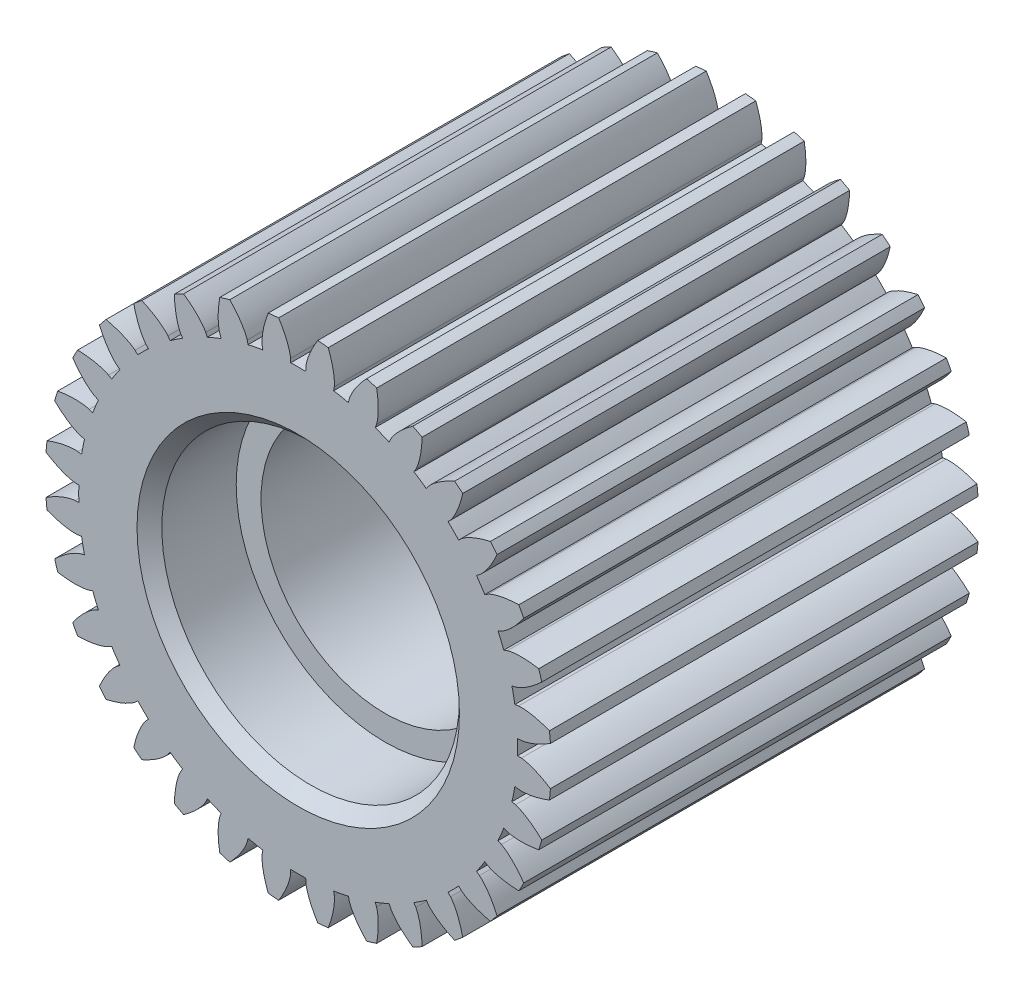
SolidWorks part; units mm, degrees
material "PLA"
ref_plane "Front Plane" through (0, 0, 0) normal (0, 0, 1) x (1, 0, 0)
ref_plane "Top Plane" through (0, 0, 0) normal (0, 1, 0) x (1, 0, 0)
ref_plane "Right Plane" through (0, 0, 0) normal (1, 0, 0) x (0, 0, -1)
sketch "Sketch1" plane through (0, 0, 0) normal (0, 0, 1) x (1, 0, 0)
  circle A0 centre (0, 0) radius 15
  dimension "D1" = 30
extrude "Boss-Extrude1" add sketch "Sketch1" along normal mid plane 17.2389
sketch "Sketch2" plane through (0, 0, 0) normal (0, 0, 1) x (1, 0, 0)
  line L0 (0, 0) -> (14.3977, 0.2566) construction
  line L1 (0, 0) -> (14.4, 0) construction
  line L2 (0, 0) -> (14.3977, -0.2566) construction
  line L3 (13.527, -0.2411) -> (13.6478, -0.2432)
  line L4 (13.5294, 0.2411) -> (13.6478, 0.2432)
  circle A0 centre (0, 0) radius 14.4 construction
  circle A1 centre (0, 0) radius 13.5316 construction
  circle A2 centre (0, 0) radius 13.65
  circle A3 centre (0, 0) radius 15 construction
  circle A4 centre (0, 0) radius 15
  spline S0 degree 4 poles (13.5294, 0.2411) (13.534, 0.2413) (13.547, 0.2419) (13.5715, 0.2439) (13.6113, 0.2483) (13.662, 0.2556) (13.7273, 0.267) (13.8039, 0.2829) (13.8878, 0.303) (13.9786, 0.3276) (14.0688, 0.3547) (14.1584, 0.3839) (14.2472, 0.4152) (14.3542, 0.4554) (14.4819, 0.507) (14.6298, 0.5722) (14.7962, 0.6518) (14.964, 0.7391) (15.1277, 0.8299) (15.2913, 0.9272) (15.4482, 1.0254) (15.6092, 1.1331) (15.7568, 1.2354) (15.9198, 1.3563) (16.0506, 1.4557) (16.2205, 1.5933) (16.32, 1.6765) (16.4355, 1.7761) (16.4863, 1.8215) (16.5176, 1.8494) knots 0 0 0 0 0 0.005377 0.015084 0.028532 0.04661 0.064855 0.092111 0.119476 0.146842 0.174209 0.201575 0.228941 0.256307 0.307035 0.361767 0.4165 0.471232 0.525964 0.580697 0.635429 0.690161 0.744894 0.799626 0.854358 0.909091 0.954545 1 1 1 1 1 construction
  spline S1 degree 4 poles (13.5294, 0.2411) (13.534, 0.2413) (13.547, 0.2419) (13.5715, 0.2439) (13.6113, 0.2483) (13.662, 0.2556) (13.7273, 0.267) (13.8039, 0.2829) (13.8878, 0.303) (13.9786, 0.3276) (14.0688, 0.3547) (14.1584, 0.3839) (14.2472, 0.4152) (14.3542, 0.4554) (14.4819, 0.507) (14.6298, 0.5722) (14.7962, 0.6518) (14.964, 0.7391) (15.1277, 0.8299) (15.2913, 0.9272) (15.4482, 1.0254) (15.6092, 1.1331) (15.7568, 1.2354) (15.9198, 1.3563) (16.0506, 1.4557) (16.1836, 1.5634) (16.2481, 1.6166) (16.2809, 1.6441) knots 0 0 0 0 0 0.005377 0.015084 0.028532 0.04661 0.064855 0.092111 0.119476 0.146842 0.174209 0.201575 0.228941 0.256307 0.307035 0.361767 0.4165 0.471232 0.525964 0.580697 0.635429 0.690161 0.744894 0.799626 0.854358 0.909091 0.909091 0.909091 0.909091 0.909091
  spline S2 degree 4 poles (13.527, -0.2411) (13.5316, -0.2412) (13.5446, -0.2419) (13.569, -0.2438) (13.6089, -0.2483) (13.6595, -0.2556) (13.7248, -0.2669) (13.8015, -0.2828) (13.8853, -0.3029) (13.9762, -0.3276) (14.0664, -0.3546) (14.1559, -0.3839) (14.2447, -0.4151) (14.3518, -0.4554) (14.4794, -0.507) (14.6274, -0.5722) (14.7937, -0.6518) (14.9616, -0.739) (15.1253, -0.8298) (15.2888, -0.9272) (15.4458, -1.0254) (15.6068, -1.1331) (15.7543, -1.2354) (15.9173, -1.3563) (16.0481, -1.4556) (16.218, -1.5932) (16.3175, -1.6764) (16.4331, -1.776) (16.4838, -1.8215) (16.5151, -1.8494) knots 0 0 0 0 0 0.005377 0.015084 0.028532 0.04661 0.064855 0.092111 0.119476 0.146842 0.174209 0.201575 0.228941 0.256307 0.307035 0.361767 0.4165 0.471232 0.525964 0.580697 0.635429 0.690161 0.744894 0.799626 0.854358 0.909091 0.954545 1 1 1 1 1 construction
  spline S3 degree 4 poles (13.527, -0.2411) (13.5316, -0.2412) (13.5446, -0.2419) (13.569, -0.2438) (13.6089, -0.2483) (13.6595, -0.2556) (13.7248, -0.2669) (13.8015, -0.2828) (13.8853, -0.3029) (13.9762, -0.3276) (14.0664, -0.3546) (14.1559, -0.3839) (14.2447, -0.4151) (14.3518, -0.4554) (14.4794, -0.507) (14.6274, -0.5722) (14.7937, -0.6518) (14.9616, -0.739) (15.1253, -0.8298) (15.2888, -0.9272) (15.4458, -1.0254) (15.6068, -1.1331) (15.7543, -1.2354) (15.9173, -1.3563) (16.0481, -1.4556) (16.1812, -1.5634) (16.2456, -1.6166) (16.2784, -1.6441) knots 0 0 0 0 0 0.005377 0.015084 0.028532 0.04661 0.064855 0.092111 0.119476 0.146842 0.174209 0.201575 0.228941 0.256307 0.307035 0.361767 0.4165 0.471232 0.525964 0.580697 0.635429 0.690161 0.744894 0.799626 0.854358 0.909091 0.909091 0.909091 0.909091 0.909091
  dimension "D1" = 28.8
  dimension "D2" = 27.0631
  dimension "D3" = 27.3
  dimension "D4" = 1.021
  dimension "D5" = 1.021
extrude "Cut-Extrude1" cut sketch "Sketch2" against normal through all both and the other way through all
pattern_circular "CirPattern2" count 48 over 360 about axis through (0, 0, 8.6195) along (0, 0, -1) of "Cut-Extrude1"
sketch "Sketch3" plane through (0, 0, 8.6195) normal (0, 0, 1) x (1, 0, 0)
  circle A0 centre (0, 0) radius 5
  dimension "D1" = 10
sketch "Sketch4" plane through (0, 0, -8.6195) normal (0, 0, -1) x (-1, 0, 0)
  circle A0 centre (0, 0) radius 10.2
  dimension "D1" = 20.4
extrude "Boss-Extrude2" add sketch "Sketch4" along normal blind 17.2389
sketch "Sketch5" plane through (0, 0, -25.8584) normal (0, 0, -1) x (-1, 0, 0)
  line L0 (0, 0) -> (10.2, 0) construction
  line L1 (0, 0) -> (10.194, 0.3486) construction
  line L2 (0, 0) -> (10.194, -0.3486) construction
  line L3 (8.9952, 0.3076) -> (8.8448, 0.3025)
  line L4 (8.9952, -0.3076) -> (8.8448, -0.3025)
  circle A0 centre (0, 0) radius 9.021 construction
  circle A1 centre (0, 0) radius 8.85
  arc A2 (10.1694, -0.7895) -> (10.1694, 0.7895) centre (0, 0) ccw
  spline S0 degree 4 poles (8.9952, 0.3076) (8.9983, 0.3078) (9.0069, 0.3083) (9.0232, 0.3099) (9.0497, 0.3133) (9.0989, 0.3212) (9.1575, 0.3334) (9.2234, 0.3498) (9.2937, 0.3702) (9.3535, 0.3892) (9.4129, 0.4097) (9.4717, 0.4314) (9.5427, 0.4594) (9.6272, 0.4952) (9.7251, 0.5403) (9.8351, 0.5952) (9.9461, 0.6552) (10.0542, 0.7175) (10.1621, 0.7842) (10.2657, 0.8513) (10.3718, 0.9249) (10.4691, 0.9947) (10.5764, 1.077) (10.6625, 1.1447) (10.7743, 1.2383) (10.8397, 1.2948) (10.9156, 1.3625) (10.9489, 1.3933) (10.9695, 1.4123) knots 0 0 0 0 0 0.005377 0.015084 0.028532 0.04661 0.092111 0.119476 0.146842 0.174209 0.201575 0.228941 0.256307 0.307035 0.361767 0.4165 0.471232 0.525964 0.580697 0.635429 0.690161 0.744894 0.799626 0.854358 0.909091 0.954545 1 1 1 1 1 construction
  spline S1 degree 4 poles (8.9952, 0.3076) (8.9983, 0.3078) (9.0069, 0.3083) (9.0232, 0.3099) (9.0497, 0.3133) (9.0989, 0.3212) (9.1575, 0.3334) (9.2234, 0.3498) (9.2937, 0.3702) (9.3535, 0.3892) (9.4129, 0.4097) (9.4717, 0.4314) (9.5427, 0.4594) (9.6272, 0.4952) (9.7251, 0.5403) (9.8351, 0.5952) (9.9461, 0.6552) (10.0542, 0.7175) (10.1621, 0.7842) (10.2657, 0.8513) (10.3718, 0.9249) (10.4691, 0.9947) (10.5764, 1.077) (10.6625, 1.1447) (10.75, 1.218) (10.7924, 1.2541) (10.814, 1.2728) knots 0 0 0 0 0 0.005377 0.015084 0.028532 0.04661 0.092111 0.119476 0.146842 0.174209 0.201575 0.228941 0.256307 0.307035 0.361767 0.4165 0.471232 0.525964 0.580697 0.635429 0.690161 0.744894 0.799626 0.854358 0.909091 0.909091 0.909091 0.909091 0.909091
  spline S2 degree 4 poles (8.9952, -0.3076) (8.9983, -0.3078) (9.0069, -0.3083) (9.0232, -0.3099) (9.0497, -0.3133) (9.0989, -0.3212) (9.1575, -0.3334) (9.2234, -0.3498) (9.2937, -0.3702) (9.3535, -0.3892) (9.4129, -0.4097) (9.4717, -0.4314) (9.5427, -0.4594) (9.6272, -0.4952) (9.7251, -0.5403) (9.8351, -0.5952) (9.9461, -0.6552) (10.0542, -0.7175) (10.1621, -0.7842) (10.2657, -0.8513) (10.3718, -0.9249) (10.4691, -0.9947) (10.5764, -1.077) (10.6625, -1.1447) (10.7743, -1.2383) (10.8397, -1.2948) (10.9156, -1.3625) (10.9489, -1.3933) (10.9695, -1.4123) knots 0 0 0 0 0 0.005377 0.015084 0.028532 0.04661 0.092111 0.119476 0.146842 0.174209 0.201575 0.228941 0.256307 0.307035 0.361767 0.4165 0.471232 0.525964 0.580697 0.635429 0.690161 0.744894 0.799626 0.854358 0.909091 0.954545 1 1 1 1 1 construction
  spline S3 degree 4 poles (8.9952, -0.3076) (8.9983, -0.3078) (9.0069, -0.3083) (9.0232, -0.3099) (9.0497, -0.3133) (9.0989, -0.3212) (9.1575, -0.3334) (9.2234, -0.3498) (9.2937, -0.3702) (9.3535, -0.3892) (9.4129, -0.4097) (9.4717, -0.4314) (9.5427, -0.4594) (9.6272, -0.4952) (9.7251, -0.5403) (9.8351, -0.5952) (9.9461, -0.6552) (10.0542, -0.7175) (10.1621, -0.7842) (10.2657, -0.8513) (10.3718, -0.9249) (10.4691, -0.9947) (10.5764, -1.077) (10.6625, -1.1447) (10.75, -1.218) (10.7924, -1.2541) (10.814, -1.2728) knots 0 0 0 0 0 0.005377 0.015084 0.028532 0.04661 0.092111 0.119476 0.146842 0.174209 0.201575 0.228941 0.256307 0.307035 0.361767 0.4165 0.471232 0.525964 0.580697 0.635429 0.690161 0.744894 0.799626 0.854358 0.909091 0.909091 0.909091 0.909091 0.909091
  dimension "D2" = 17.7
  dimension "D3" = 20.4
  dimension "D1" = 18.0421
  dimension "D4" = 1.959
  dimension "D5" = 1.959
extrude "Cut-Extrude2" cut sketch "Sketch5" against normal up to surface (17.2389 mm away)
pattern_circular "CirPattern3" count 32 over 360 about axis through (0, 0, -25.8584) along (0, 0, 1) of "Cut-Extrude2"
extrude "Cut-Extrude3" cut sketch "Sketch3" against normal through all contours A0
sketch "Sketch7" plane through (0, 0, -25.8584) normal (0, 0, -1) x (-1, 0, 0)
  circle A0 centre (0, 0) radius 6
  dimension "D1" = 12
extrude "Cut-Extrude4" cut sketch "Sketch7" against normal blind 3.5
ref_plane "Plane1" through (0, 0, -8.6195) normal (0, 0, -1) x (-1, 0, 0)
mirror "Mirror1" [suppressed] about plane through (0, 0, -8.6195) normal (0, 0, -1)
sketch "Sketch8" plane through (0, 0, 8.6195) normal (0, 0, 1) x (1, 0, 0)
  circle A0 centre (0, 0) radius 16.2595
extrude "Cut-Extrude5" cut sketch "Sketch8" against normal up to surface (17.2389 mm away) up to face at (0, 0, -8.6195)
ref_plane "Plane2" through (0, 0, -17.2389) normal (0, 0, -1) x (-1, 0, 0)
mirror "Mirror3" about plane through (0, 0, -17.2389) normal (0, 0, -1) of "Cut-Extrude4"
chamfer "Chamfer1" distance 0.5 angle 45 2 edges at (-6, 0, -25.8584) (-6, 0, -8.6195)
equation "\"module\" = 0.6"
equation "\"pressure angle\" = 20.0"
equation "\"h_a\" = 0.6"
equation "\"h_b\" = 0.75"
equation "\"clr_tip_root\" = 0.15000000000000002"
equation "\"D1@Sketch1\" = \"dp_p_b\" + 2 * \"h_a\""
equation "\"D1@Boss-Extrude1\"=\"fw_idler\""
equation "\"D1@Sketch2\" = \"dp_p_b\""
equation "\"D2@Sketch2\"= \"db_p_b\""
equation "\"D3@Sketch2\" = \"dp_p_b\" - 2 * \"h_b\""
equation "\"Nr_s\" = 128"
equation "\"pressure_angle\" = 20.0"
equation "\"h_f\" = 0.75"
equation "\"dp_r_s\" = 76.8"
equation "\"bearing_ID\" = 65"
equation "\"bearing_OD\" = 85"
equation "\"bearing_height\" = 10"
equation "\"clearance_planet\" = 1.5"
equation "\"case_dist\" = 6.5"
equation "\"Motor_case_OD_max\" = 131.3"
equation "\"case_mounting_PCD\" = 123.8"
equation "\"bearing mount thickness\" = 8"
equation "\"case_mounting_hole_dia\" = 3"
equation "\"output_mounting_PCD\" = 93"
equation "\"output_mounting_hole_dia\" = 4"
equation "\"clearance_case_mount_holes_shell_thickness\" = 1"
equation "\"motor_case_OD_base\" = 121.8"
equation "\"sec_carrier_thickness\" = 5"
equation "\"sun_coupler_hub_thickness\" = 4"
equation "\"clearance_sun_coupler_sec_carrier\" = 1.5"
equation "\"clearance_motor_and_case\" = 5"
equation "\"motor_OD\" = 106.8"
equation "\"Motor_case_thickness\" = 2.5"
equation "\"Motor_case_ID\" = 116.8"
equation "\"case_mounting_hole_shift\" = 1.0"
equation "\"output_mounting_nut_wrench_size\" = 7"
equation "\"output_mounting_nut_thickness\" = 3.2"
equation "\"case_mounting_hole_allen_socket_dia\" = 5.5"
equation "\"output_mounting_nut_depth\" = 3"
equation "\"case_mounting_bolt_depth\" = 4.5"
equation "\"Ns\" = 48"
equation "\"ring_radial_thickness\" = 5"
equation "\"ring_to_chamfer_clearance\" = 1.5"
equation "\"Motor_case_OD_base_to_chamfer\" = 5"
equation "\"pattern_offset_from_motor_case_OD_base\" = 3"
equation "\"pattern_bulge_dia\" = 3"
equation "\"pattern_num_bulge\" = 18"
equation "\"pattern_depth\" = 2"
equation "\"motor_height\" = 47.6"
equation "\"case_mounting_wrench_size\" = 5.5"
equation "\"case_mounting_nut_clearance\" = 2"
equation "\"base_plate_thickness\" = 4"
equation "\"case_mounting_nut_thickness\" = 2.4"
equation "\"case_mounting_surface_height\" = 4"
equation "\"motor_mount_hole_PCD\" = 40"
equation "\"motor_mount_hole_dia\" = 5"
equation "\"motor_mount_hole_num\" = 4"
equation "\"central_hole_offset_from_motor_mount_PCD\" = 5"
equation "\"wire_slot_dist_from_center\" = 45.5"
equation "\"wire_slot_length\" = 10"
equation "\"wire_slot_radius\" = 3"
equation "\"driver_upper_holes_dist_from_center\" = 29"
equation "\"driver_lower_holes_dist_from_center\" = 13"
equation "\"driver_side_holes_dist_from_center\" = 22.5"
equation "\"driver_mount_holes_dia\" = 3"
equation "\"driver_mount_inserts_OD\" = 4.8"
equation "\"driver_mount_thickness\" = 1.5"
equation "\"driver_mount_height\" = 6"
equation "\"air_flow_hole_offset\" = 3"
equation "\"num_planet\" = 4"
equation "\"planet_pin_bolt_dia\" = 5"
equation "\"planet_pin_socket_head_dia\" = 8.5"
equation "\"carrier_PCD\" = 57.599999999999994"
equation "\"planet_shaft_dia\" = 8"
equation "\"planet_shaft_step_offset\" = 1"
equation "\"carrier_trapezoidal_support_sun_offset\" = 5"
equation "\"carrier_trapezoidal_support_hole_PCD_offset_bearing_ID\" = 4"
equation "\"carrier_trapezoidal_support_hole_dia\" = 3"
equation "\"carrier_trapezoidal_support_hole_socket_head_dia\" = 5.5"
equation "\"carrier_bearing_step_width\" = 1.5"
equation "\"standard_clearance_1_5mm\" = 1.5"
equation "\"standard_fillet_1_5mm\" = 1.5"
equation "\"sun_shaft_bearing_OD\" = 16"
equation "\"sun_shaft_bearing_width\" = 5"
equation "\"standard_bearing_insertion_chamfer\" = 0.5"
equation "\"carrier_trapezoidal_support_hole_wrench_size\" = 5.5"
equation "\"planet_pin_bolt_wrench_size\" = 8"
equation "\"planet_bearing_OD\" = 12"
equation "\"planet_bearing_width\" = 3.5"
equation "\"planet_bore\" = 10"
equation "\"D1@Sketch3\"=\"planet_bore\""
equation "\"Np_b\" = 48"
equation "\"dp_s\" = 28.799999999999997"
equation "\"db_s\" = 27.06314747863416"
equation "\"fw_s_calc\" = 7.664359769718526"
equation "\"alpha_s\" = 0.8539582918412343"
equation "\"beta_s\" = 2.0420834163175314"
equation "\"dp_p_b\" = 28.799999999999997"
equation "\"db_p_b\" = 27.06314747863416"
equation "\"fw_p_s\" = 30.231545005724083"
equation "\"alpha_p_b\" = 0.8539582918412343"
equation "\"beta_p_b\" = 2.0420834163175314"
equation "\"motor_output_hole_PCD\" = 23"
equation "\"motor_output_hole_dia\" = 4"
equation "\"motor_output_hole_num\" = 4"
equation "\"sun_shaft_bearing_ID\" = 8"
equation "\"sun_hub_dia\" = 30.0"
equation "\"sun_central_bolt_dia\" = 5"
equation "\"sun_central_bolt_socket_head_dia\" = 8.5"
equation "\"fw_s_used\" = 72.54334182621932"
equation "\"motor_output_hole_CSK_OD\" = 8"
equation "\"motor_output_hole_CSK_head_height\" = 2.0"
equation "\"bearing_retainer_thickness\" = 2"
equation "\"Np_s\" = 32"
equation "\"fw_p_b\" = 34.81179682049524"
equation "\"dp_p_s\" = 19.2"
equation "\"db_p_s\" = 18.04209831908944"
equation "\"alpha_p_s\" = 0.8539582918412556"
equation "\"beta_p_s\" = 3.917083416317489"
equation "\"D1@Sketch4\"=\"dp_p_s\" + 2 * \"h_a\""
equation "\"D1@Boss-Extrude2\"=\"fw_idler\""
equation "\"D2@Sketch5\"=\"dp_p_s\" - 2 * \"h_b\""
equation "\"D3@Sketch5\"=\"dp_p_s\"+2 * \"h_a\" "
equation "\"D1@Sketch5\"=\"db_p_s\""
equation "\"D1@CirPattern3\"=\"Np_s\""
equation "\"D4@Sketch5\"=\"beta_p_s\"/2"
equation "\"D5@Sketch5\"=\"beta_p_s\"/2"
equation "\"D4@Sketch2\"=\"beta_p_b\"/2"
equation "\"D5@Sketch2\"=\"beta_p_b\"/2"
equation "\"D1@Sketch7\"=\"planet_bearing_OD\""
equation "\"D1@Cut-Extrude4\"=\"planet_bearing_width\""
equation "\"D1@Chamfer1\"=\"standard_bearing_insertion_chamfer\""
equation "\"D1@CirPattern2\"=\"Np_b\""
equation "\"Nr_b\" = 144"
equation "\"dp_r_b\" = 86.39999999999999"
equation "\"db_r_b\" = 81.18944243590248"
equation "\"fw_r_b\" = 34.81179682049524"
equation "\"alpha_r_b\" = 0.8539582918412414"
equation "\"beta_r_b\" = 2.957916583682483"
equation "\"ring_OD_b\" = 96.39999999999999"
equation "\"Fillet10\"= IIF ( \"ring_OD_b\" > ( \"bearing_OD\" + 2 * \"bearing mount thickness\" ) , \"suppressed\" , \"unsuppressed\" )"
equation "\"Fillet11\"= IIF ( \"ring_OD_b\" < ( \"bearing_OD\" + 2 * \"bearing mount thickness\" ) , \"suppressed\" , \"unsuppressed\" )"
equation "\"clr_tip_root_s\" = 0.15000000000000002"
equation "\"db_r_s\" = 72.16839327635776"
equation "\"fw_r_s\" = 28.731545005724083"
equation "\"alpha_r_s\" = 0.8539582918412556"
equation "\"beta_r_s\" = 3.114166583682511"
equation "\"small_ring_case_thickness\" = 4"
equation "\"carrier_thickness\" = 4"
equation "\"small_ring_output_wall_thickness\" = 5"
equation "\"small_ring_output_wall_to_bearing_shaft_attachement_hole_dia\" = 4"
equation "\"small_ring_output_wall_to_bearing_shaft_attachement_hole_depth\" = 6.5"
equation "\"small_ring_output_wall_to_bearing_shaft_attachement_nut_wrench\" = 7"
equation "\"small_ring_output_wall_to_bearing_shaft_attachement_nut_thickness\" = 3.2"
equation "\"small_ring_output_wall_to_bearing_shaft_attachement_hole_pcd\" = 12"
equation "\"small_ring_output_wall_to_bearing_shaft_attachement_hole_num\" = 3"
equation "\"small_ring_output_wall_to_bearing_shaft_attachement_hole_CSK_OD\" = 8"
equation "\"small_ring_output_wall_to_bearing_shaft_attachement_hole_CSK_head_height\" = 2.0"
equation "\"carrier_small_ring_inner_bearing_ID\" = 20"
equation "\"carrier_small_ring_inner_bearing_OD\" = 32"
equation "\"carrier_small_ring_inner_bearing_height\" = 7"
equation "\"carrier_small_ring_inner_bearing_flap\" = 2"
equation "\"gear_casing_big_ring_to_bearing_dist\" = 39.23154500572409"
equation "\"gear_casing_thickness\" = 4"
equation "\"tight_clearance_3DP\" = 0.4"
equation "\"loose_clearance_3DP\" = 0.8"
equation "\"Ns_fs\" = 64"
equation "\"dp_fs\" = 38.4"
equation "\"db_fs\" = 36.08419663817888"
equation "\"alpha_fs\" = 0.8539582918412556"
equation "\"beta_fs\" = 1.1045834163174888"
equation "\"fw_fs\" = 30.231545005724083"
equation "\"num_idler\" = 4"
equation "\"idler_angle_offset\" = 45.0"
equation "\"fs_bore_dia\" = 31.599999999999998"
equation "\"fs_bore_wall\" = 2.6500000000000004"
equation "\"fs_axial_clearance\" = 0.8"
equation "\"fw_idler\" = 17.23892700343445"
